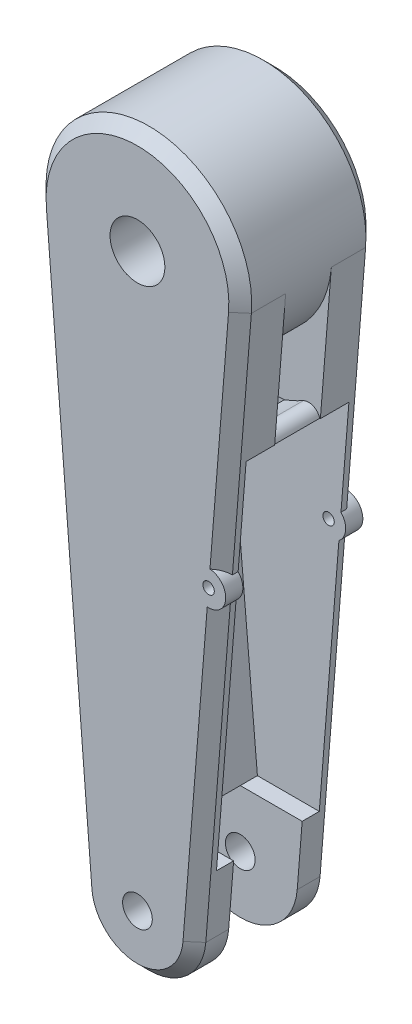
SolidWorks part; units mm, degrees
ref_plane "Front Plane" through (0, 0, 0) normal (0, 0, 1) x (1, 0, 0)
ref_plane "Top Plane" through (0, 0, 0) normal (0, 1, 0) x (1, 0, 0)
ref_plane "Right Plane" through (0, 0, 0) normal (1, 0, 0) x (0, 0, -1)
sketch "Sketch1" plane through (0, 0, 0) normal (0, 0, 1) x (1, 0, 0)
  circle A0 centre (0, 0) radius 45
  circle A1 centre (0, 0) radius 12
  dimension "D1" = 90
  dimension "D2" = 24
extrude "Boss-Extrude1" add sketch "Sketch1" along normal mid plane 60
sketch "Sketch2" plane through (0, 0, 30) normal (0, 0, 1) x (1, 0, 0)
  line L0 (0, 0) -> (0, -250) construction
  line L1 (-44.8558, -3.6) -> (-24.9199, -252)
  line L2 (24.9199, -252) -> (44.8558, -3.6)
  arc A0 (-24.9199, -252) -> (24.9199, -252) centre (0, -250) ccw
  circle A1 centre (0, 0) radius 45 construction
  arc A2 (-44.8558, -3.6) -> (44.8558, -3.6) centre (0, 0) ccw
  circle A3 centre (0, -250) radius 6.5
  dimension "D2" = 50
  dimension "D3" = 13
  dimension "D1" = 250
extrude "Boss-Extrude2" add sketch "Sketch2" against normal blind 60
ref_plane "Plane2" through (0, 0, 0) normal (0, 0, 1) x (1, 0, 0)
sketch "Sketch3" plane through (0, 0, 0) normal (0, 0, 1) x (1, 0, 0)
  line L0 (-44.8558, -3.6) -> (-24.9199, -252) construction
  line L1 (24.9199, -252) -> (44.8558, -3.6) construction
  line L2 (-27.0868, -225) -> (-24.9199, -252)
  line L3 (24.9199, -252) -> (27.0868, -225)
  line L4 (27.0868, -225) -> (-27.0868, -225)
  arc A0 (-24.9199, -252) -> (24.9199, -252) centre (0, -250) ccw construction
  arc A1 (-24.9199, -252) -> (24.9199, -252) centre (0, -250) ccw
  dimension "D1" = 25
extrude "Cut-Extrude1" cut sketch "Sketch3" against normal mid plane 30
chamfer "Chamfer1" distance 5 angle 45 8 edges at (34.8878, -127.8, -30) (0, 45, -30) (0, -275, -30) (-34.8878, -127.8, -30) (34.8878, -127.8, 30) (0, 45, 30) (0, -275, 30) (-34.8878, -127.8, 30)
ref_plane "Plane3" through (0, 0, 0) normal (0, 0, 1) x (1, 0, 0)
sketch "Sketch4" plane through (0, 0, 0) normal (0, 0, 1) x (1, 0, 0)
  line L0 (44.8558, -3.6) -> (24.9199, -252) construction
  line L1 (-24.9199, -252) -> (-44.8558, -3.6) construction
  line L2 (44.8558, -3.6) -> (24.9199, -252) construction
  line L3 (-24.9199, -252) -> (-44.8558, -3.6) construction
  arc A0 (44.8558, -3.6) -> (-44.8558, -3.6) centre (0, 0) ccw construction
  arc A1 (44.8558, -3.6) -> (-44.8558, -3.6) centre (0, 0) ccw
  circle A2 centre (0, 0) radius 45
  circle A3 centre (0, 0) radius 68.5703
  arc A4 (-46.8261, 26.1008) -> (46.8261, -8.9603) centre (0, 8.5703) ccw construction
  dimension "D1" = 10
extrude "Cut-Extrude3" cut sketch "Sketch4" against normal mid plane 20 contours A3 A2 A1 region at (-66.6308, 0, 0)
fillet "Fillet1" radius 5 2 edges at (40.7167, -55.1728, 0) (-40.7167, -55.1728, 0)
sketch "Sketch5" plane through (0, 0, 0) normal (0, 0, 1) x (1, 0, 0)
  line L0 (19.9359, -251.6) -> (39.8718, -3.2) construction
  line L1 (19.9359, -251.6) -> (39.8718, -3.2) construction
  circle A0 centre (31.1359, -112.0487) radius 2.5
  dimension "D1" = 5
  dimension "D2" = 140
extrude "Cut-Extrude4" cut sketch "Sketch5" against normal through all both and the other way through all
sketch "Sketch6" plane through (0, 0, 0) normal (0, 0, 1) x (1, 0, 0)
  arc A0 (31.3359, -109.5567) -> (30.9359, -114.5407) centre (31.1359, -112.0487) ccw construction
  arc A1 (31.3359, -109.5567) -> (30.9359, -114.5407) centre (31.1359, -112.0487) ccw construction
  circle A2 centre (31.1359, -112.0487) radius 2.5
  circle A3 centre (31.1359, -112.0487) radius 7.5
  dimension "D1" = 15
extrude "Boss-Extrude3" add sketch "Sketch6" along normal through all and the other way through all
sketch "Sketch8" plane through (0, 0, 0) normal (0, 0, 1) x (1, 0, 0)
  line L0 (31.7359, -104.5728) -> (39.8718, -3.2) construction
  line L1 (31.7359, -104.5728) -> (39.8718, -3.2) construction
  line L2 (44.8558, -3.6) -> (36.5671, -106.8765) construction
  line L3 (44.8558, -3.6) -> (36.5671, -106.8765) construction
  line L4 (39.6558, -68.3917) -> (0, -65.209) construction
  line L5 (0, -65.209) -> (0, -225) construction
  line L7 (39.6558, -225) -> (39.6558, -68.3917)
  line L8 (27.0868, -225) -> (-27.0868, -225) construction
  line L9 (27.0868, -225) -> (0, -225)
  line L10 (27.0868, -225) -> (39.6558, -225)
  line L11 (0, -65.209) -> (40.0558, -63.4077)
  line L12 (40.0558, -63.4077) -> (39.6558, -68.3917)
  line L13 (0, -225) -> (-13.9799, -65.209)
  line L14 (-13.9799, -65.209) -> (0, -65.209)
  dimension "D1" = 65
  dimension "D2" = 5
  dimension "D3" = 175
extrude "Cut-Extrude5" cut sketch "Sketch8" against normal mid plane 45
equation "\"Outer Knee Width\"=90"
equation "\"D1@Sketch1\"=\"Outer Knee Width\""
